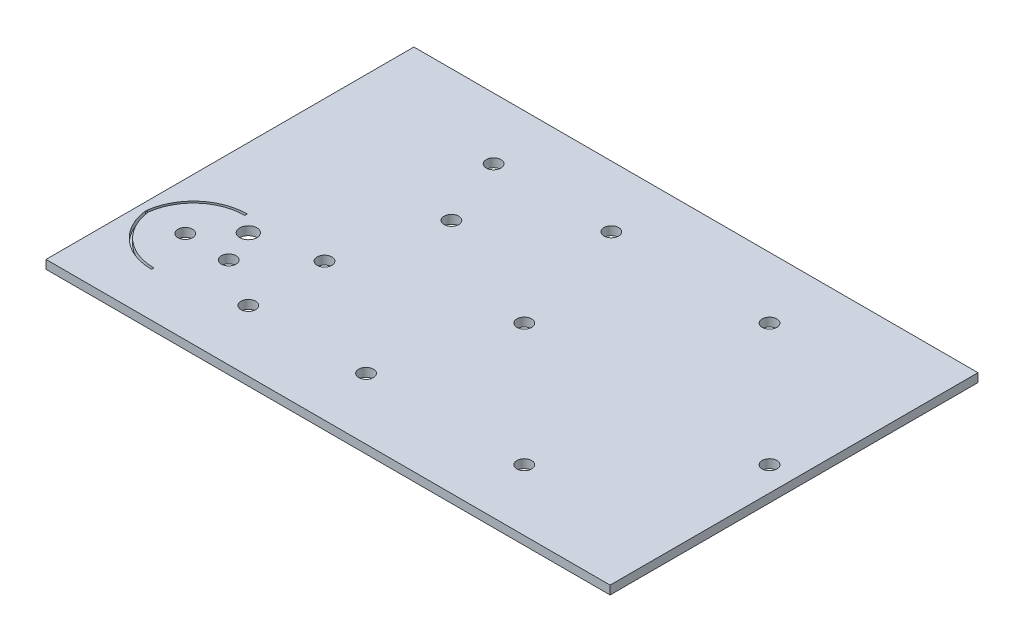
SolidWorks part; units mm, degrees
ref_plane "前基準面" through (0, 0, 0) normal (0, 0, 1) x (1, 0, 0)
ref_plane "上基準面" through (0, 0, 0) normal (0, 1, 0) x (1, 0, 0)
ref_plane "右基準面" through (0, 0, 0) normal (1, 0, 0) x (0, 0, -1)
sketch "草圖1" plane through (0, 0, 0) normal (0, 1, 0) x (1, 0, 0)
  line L0 (0, 0) -> (0, 112.1795) construction
  line L1 (-190, 75) -> (60, 75)
  line L2 (-190, 75) -> (-190, -75)
  line L3 (-190, -75) -> (60, -75)
  line L4 (60, 75) -> (60, -75)
  line L5 (0, 0) -> (222.1154, 0) construction
  line L6 (0, 0) -> (0, -82.367) construction
  line L7 (0, 0) -> (-107.6818, 0) construction
  circle A0 centre (0, 0) radius 50 construction
  circle A1 centre (0, 50) radius 3
  circle A2 centre (50, 0) radius 3
  circle A3 centre (-50, 0) radius 3
  circle A4 centre (0, -50) radius 3
  dimension "D4" = 100
  dimension "D5" = 6
  dimension "D6" = 6
  dimension "D7" = 6
  dimension "D8" = 6
  dimension "D1" = 250
  dimension "D2" = 60
  dimension "D3" = 150
extrude "填料-伸長1" add sketch "草圖1" against normal blind 5 contours L3 L4 L1 L2
extrude "除料-伸長1" cut sketch "草圖1<4>" against normal blind 5 contours A1
sketch "草圖1<4>" plane through (0, 0, 0) normal (0, 1, 0) x (1, 0, 0) same geometry as "草圖1"
extrude "除料-伸長2" cut sketch "草圖1<5>" against normal blind 5 contours A3
sketch "草圖1<5>" plane through (0, 0, 0) normal (0, 1, 0) x (1, 0, 0) same geometry as "草圖1"
extrude "除料-伸長3" cut sketch "草圖1<6>" against normal blind 5 contours A4
sketch "草圖1<6>" plane through (0, 0, 0) normal (0, 1, 0) x (1, 0, 0) same geometry as "草圖1"
extrude "除料-伸長4" cut sketch "草圖1<7>" against normal blind 5 contours A2
sketch "草圖1<7>" plane through (0, 0, 0) normal (0, 1, 0) x (1, 0, 0) same geometry as "草圖1"
sketch "草圖2" plane through (0, 0, 0) normal (0, 1, 0) x (1, 0, 0)
  line L0 (-190, -75) -> (60, -75) construction
  line L1 (-190, 75) -> (-190, -75) construction
  circle A0 centre (-150.76, -37.46) radius 3
  dimension "D1" = 6
  dimension "D2" = 37.54
  dimension "D3" = 39.24
extrude "除料-伸長5" cut sketch "草圖2" against normal blind 5
sketch "草圖3" plane through (0, 0, 0) normal (0, 1, 0) x (1, 0, 0)
  line L0 (-190, 75) -> (-190, -75) construction
  line L1 (-190, -75) -> (60, -75) construction
  circle A0 centre (-138.16, -24.34) radius 3.5
  circle A1 centre (-132.57, -37.93) radius 3
  dimension "D1" = 7
  dimension "D2" = 6
  dimension "D3" = 57.43
  dimension "D4" = 37.07
  dimension "D5" = 51.84
  dimension "D6" = 50.66
extrude "除料-伸長6" cut sketch "草圖3" against normal blind 45 contours A1
extrude "除料-伸長7" cut sketch "草圖3<3>" against normal blind 45 contours A0
sketch "草圖3<3>" plane through (0, 0, 0) normal (0, 1, 0) x (1, 0, 0) same geometry as "草圖3"
sketch "草圖4" plane through (0, 0, 0) normal (0, 1, 0) x (1, 0, 0)
  circle A0 centre (-64.5, -50) radius 3
  circle A1 centre (-112.5, -50) radius 3
  circle A2 centre (0, -50) radius 3 construction
  circle A3 centre (0, -50) radius 3
  dimension "D1" = 6
  dimension "D2" = 6
  dimension "D3" = 64.5
  dimension "D4" = 48
extrude "除料-伸長8" cut sketch "草圖4" against normal blind 5 contours A1
extrude "除料-伸長9" cut sketch "草圖4<3>" against normal blind 5 contours A0
sketch "草圖4<3>" plane through (0, 0, 0) normal (0, 1, 0) x (1, 0, 0) same geometry as "草圖4"
sketch "草圖5" plane through (0, 0, 0) normal (0, 1, 0) x (1, 0, 0)
  line L0 (-190, 75) -> (-190, -75) construction
  line L2 (-190, -75) -> (60, -75) construction
  circle A0 centre (-112.61, -18.84) radius 3
  circle A1 centre (-101.14, 21.42) radius 3
  dimension "D1" = 6
  dimension "D2" = 6
  dimension "D3" = 77.39
  dimension "D4" = 56.16
  dimension "D5" = 11.47
  dimension "D6" = 40.26
extrude "除料-伸長10" cut sketch "草圖5" against normal blind 5
sketch "草圖6" plane through (0, 0, 0) normal (0, 1, 0) x (1, 0, 0)
  line L4 (-190, 75) -> (-190, -75)
  line L5 (-190, -75) -> (60, -75)
  line L6 (60, -75) -> (60, 75)
  line L7 (60, 75) -> (-190, 75)
  line L8 (-190, 75) -> (-190, -75)
  line L9 (-190, -75) -> (60, -75)
  line L10 (60, -75) -> (60, 75)
  line L11 (60, 75) -> (-190, 75)
  circle A0 centre (-150.76, -37.46) radius 3 construction
  circle A1 centre (-138.16, -24.34) radius 3.5 construction
  circle A2 centre (-132.57, -37.93) radius 3 construction
  circle A3 centre (-112.61, -18.84) radius 3 construction
  circle A4 centre (-112.5, -50) radius 3 construction
  circle A5 centre (-101.14, 21.42) radius 3 construction
  circle A6 centre (-50, 0) radius 3 construction
  circle A7 centre (-64.5, -50) radius 3 construction
  circle A8 centre (0, 50) radius 3 construction
  circle A9 centre (0, -50) radius 3 construction
  circle A10 centre (50, 0) radius 3 construction
  circle A11 centre (-150.76, -37.46) radius 3
  circle A12 centre (-138.16, -24.34) radius 3.5
  circle A13 centre (-132.57, -37.93) radius 3
  circle A14 centre (-112.61, -18.84) radius 3
  circle A15 centre (-112.5, -50) radius 3
  circle A16 centre (-101.14, 21.42) radius 3
  circle A17 centre (-50, 0) radius 3
  circle A18 centre (-64.5, -50) radius 3
  circle A19 centre (0, 50) radius 3
  circle A20 centre (0, -50) radius 3
  circle A21 centre (50, 0) radius 3
  dimension "D1" = 0
extrude "除料-伸長11" cut sketch "草圖6" against normal blind 1.5
sketch "草圖7" plane through (0, -1.5, 0) normal (0, 1, 0) x (1, 0, 0)
  line L0 (0, 50) -> (-157.2363, 50) construction
  circle A0 centre (-64.5, 50) radius 3
  circle A1 centre (-112.5, 50) radius 3
  circle A2 centre (-64.5, -50) radius 3 construction
  circle A3 centre (-112.5, -50) radius 3 construction
  circle A4 centre (-64.5, -50) radius 3
  circle A5 centre (-112.5, -50) radius 3
  dimension "D1" = 64.5
  dimension "D3" = 6
  dimension "D4" = 6
  dimension "D2" = 48
extrude "除料-伸長12" cut sketch "草圖7" against normal through all
sketch "草圖8" plane through (0, -1.5, 0) normal (0, 1, 0) x (1, 0, 0)
  line L0 (-190, 75) -> (-190, -75) construction
  line L1 (-252.6218, 90.7473) -> (-170, 90.7473)
  line L2 (-252.6218, 90.7473) -> (-252.6218, -90.5617)
  line L3 (-252.6218, -90.5617) -> (-170, -90.5617)
  line L4 (-170, 90.7473) -> (-170, -90.5617)
  dimension "D1" = 20
extrude "除料-伸長13" cut sketch "草圖8" against normal blind 10
sketch "草圖11" plane through (0, -1.5, 0) normal (0, 1, 0) x (1, 0, 0)
  line L2 (-165.8491, -37.5128) -> (-166.8419, -37.6325)
  line L3 (-145, -56) -> (-145, -57)
  arc A0 (-165.8491, -37.5128) -> (-145, -56) centre (-145, -35) ccw
  arc A1 (-166.8419, -37.6325) -> (-145, -57) centre (-145, -35) ccw
  circle A3 centre (-145, -35) radius 21 construction
  circle A4 centre (-145, -35) radius 22 construction
  point P1 (-123, -35)
  point P15 (-124.9176, -28.8602)
extrude "除料-伸長14" cut sketch "草圖11" against normal blind 2
ref_plane "平面1" through (0, 0, 37.46) normal (0, 0, 1) x (1, 0, 0)
mirror "鏡射1" about plane through (0, 0, 37.46) normal (0, 0, 1) of "除料-伸長14"
